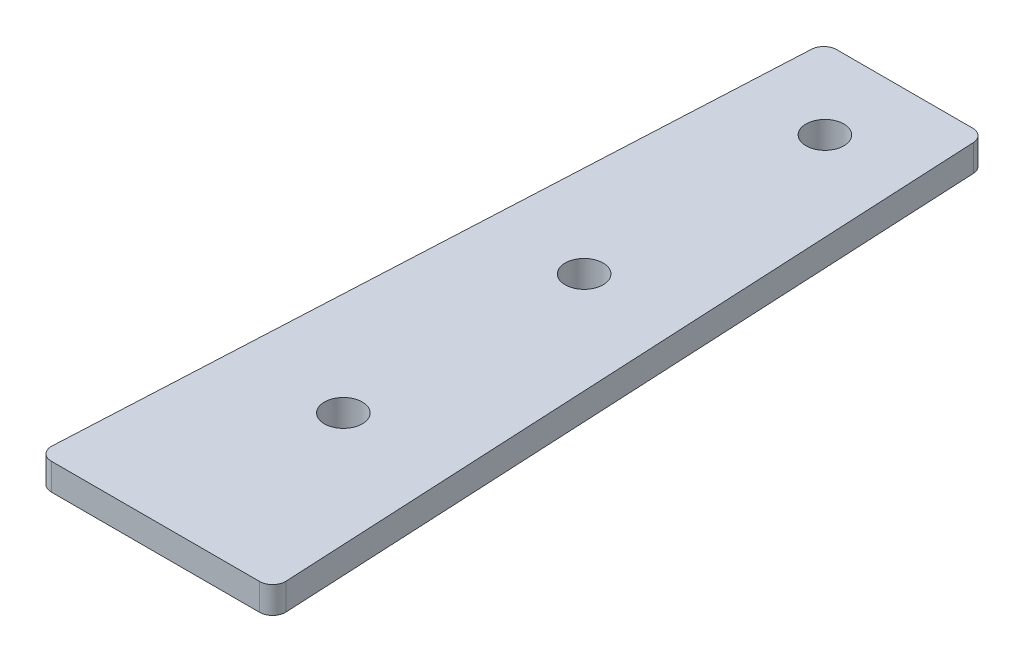
SolidWorks part; units mm, degrees
material "Custom Plastic"
ref_plane "X-Y Datum" through (0, 0, 0) normal (0, 0, 1) x (1, 0, 0)
ref_plane "X-Z Datum" through (0, 0, 0) normal (0, 1, 0) x (1, 0, 0)
ref_plane "Y-Z Datum" through (0, 0, 0) normal (1, 0, 0) x (0, 0, -1)
sketch "Sketch1" plane through (0, 0, 0) normal (0, 1, 0) x (1, 0, 0)
  line L0 (-91.83, 0) -> (49908.17, 0) construction
  line L1 (-91.83, 38.035) -> (91.83, 38.035) construction
  line L2 (-91.83, 38.035) -> (-91.83, -38.035) construction
  line L3 (-91.83, -38.035) -> (91.83, -38.035) construction
  line L4 (91.83, 38.035) -> (91.83, -38.035) construction
  line L5 (-91.83, 38.035) -> (91.83, -38.035) construction
  line L6 (-91.83, -38.035) -> (91.83, 38.035) construction
  line L7 (-115.0883, 28.575) -> (49884.9117, 28.575) construction
  line L8 (-116.2913, -28.575) -> (49883.7087, -28.575) construction
  line L9 (-75.32, 54.5103) -> (-75.32, -49945.4897) construction
  line L10 (75.32, 62.9314) -> (75.32, -49937.0686) construction
  line L11 (-75.32, 38.035) -> (-67.2447, 38.035)
  line L12 (-75.32, 38.035) -> (-83.3953, 38.035)
  line L14 (-75.32, -50.865) -> (-62.9521, -50.865)
  line L15 (-75.32, -50.865) -> (-87.6879, -50.865)
  line L16 (-84.9174, 36.5871) -> (-89.21, -49.2649)
  line L17 (-65.7226, 36.5871) -> (-61.43, -49.2649)
  arc A0 (-62.9521, -50.865) -> (-61.43, -49.2649) centre (-62.9521, -49.341) ccw
  arc A1 (-87.6879, -50.865) -> (-89.21, -49.2649) centre (-87.6879, -49.341) cw
  arc A2 (-67.2447, 38.035) -> (-65.7226, 36.5871) centre (-67.2447, 36.511) cw
  arc A3 (-83.3953, 38.035) -> (-84.9174, 36.5871) centre (-83.3953, 36.511) ccw
  point P0 (0, 0)
  point P8 (-91.83, 0)
  point P25 (-61.35, -50.865)
  point P28 (-89.29, -50.865)
  point P31 (-65.795, 38.035)
  point P34 (-84.845, 38.035)
  dimension "D12" = 1.524
  dimension "D1" = 183.66
  dimension "D2" = 76.07
  dimension "D3" = 28.575
  dimension "D4" = 28.575
  dimension "D5" = 16.51
  dimension "D6" = 16.51
  dimension "D7" = 9.525
  dimension "D8" = 9.525
  dimension "D9" = 88.9
  dimension "D10" = 13.97
  dimension "D11" = 13.97
extrude "Boss-Extrude1" add sketch "Sketch1" along normal blind 3.175
sketch "Sketch4" plane through (0, 0, 0) normal (0, 1, 0) x (1, 0, 0)
  line L0 (-91.83, 0) -> (49908.17, 0) construction
  line L1 (-91.83, 38.035) -> (91.83, 38.035) construction
  line L2 (-91.83, 38.035) -> (-91.83, -38.035) construction
  line L3 (-91.83, -38.035) -> (91.83, -38.035) construction
  line L4 (91.83, 38.035) -> (91.83, -38.035) construction
  line L5 (-91.83, 38.035) -> (91.83, -38.035) construction
  line L6 (-91.83, -38.035) -> (91.83, 38.035) construction
  line L7 (-115.0883, 28.575) -> (49884.9117, 28.575) construction
  line L8 (-116.2913, -28.575) -> (49883.7087, -28.575) construction
  line L9 (-75.32, 54.5103) -> (-75.32, -49945.4897) construction
  line L10 (75.32, 62.9314) -> (75.32, -49937.0686) construction
  line L11 (-75.32, 38.035) -> (-67.2447, 38.035)
  line L12 (-75.32, 38.035) -> (-83.3953, 38.035)
  line L14 (-75.32, -50.865) -> (-62.9521, -50.865)
  line L15 (-75.32, -50.865) -> (-87.6879, -50.865)
  line L16 (-84.9174, 36.5871) -> (-89.21, -49.2649)
  line L17 (-65.7226, 36.5871) -> (-61.43, -49.2649)
  arc A0 (-62.9521, -50.865) -> (-61.43, -49.2649) centre (-62.9521, -49.341) ccw
  arc A1 (-87.6879, -50.865) -> (-89.21, -49.2649) centre (-87.6879, -49.341) cw
  arc A2 (-67.2447, 38.035) -> (-65.7226, 36.5871) centre (-67.2447, 36.511) cw
  arc A3 (-83.3953, 38.035) -> (-84.9174, 36.5871) centre (-83.3953, 36.511) ccw
  point P0 (0, 0)
  point P8 (-91.83, 0)
  point P25 (-61.35, -50.865)
  point P28 (-89.29, -50.865)
  point P31 (-65.795, 38.035)
  point P34 (-84.845, 38.035)
  dimension "D12" = 1.524
  dimension "D1" = 183.66
  dimension "D2" = 76.07
  dimension "D3" = 28.575
  dimension "D4" = 28.575
  dimension "D5" = 16.51
  dimension "D6" = 16.51
  dimension "D7" = 9.525
  dimension "D8" = 9.525
  dimension "D9" = 88.9
  dimension "D10" = 13.97
  dimension "D11" = 13.97
hole_wizard "M4 Clearance Hole1" positions "Sketch5" profile "Sketch6" hole size "M4" standard "ANSI Metric" end condition through all
sketch "Sketch5" plane through (0, 3.175, 0) normal (0, 1, 0) x (1, 0, 0)
  line L0 (-200115.0883, 28.575) -> (249884.9117, 28.575) construction
  line L1 (-75.32, 200054.5103) -> (-75.32, -249945.4897) construction
  line L2 (-200091.83, 0) -> (249908.17, 0) construction
  line L3 (-200116.2913, -28.575) -> (249883.7087, -28.575) construction
  point P0 (-75.32, 28.575)
  point P6 (-75.32, 0)
  point P10 (-75.32, -28.575)
sketch "Sketch6" plane through (-75.32, 3.175, -28.575) normal (1, 0, 0) x (0, 0, 1)
  line L0 (0, 0) -> (0, 3.175)
  line L1 (0, 3.175) -> (2.25, 3.175)
  line L2 (2.25, 3.175) -> (2.25, 0)
  line L5 (2.25, 0) -> (0, 0)
  line L11 (0, -6.35) -> (0, 107.95) construction
  dimension "Thru Hole Dia." = 4.5
  dimension "Thru Hole Depth" = 3.175
